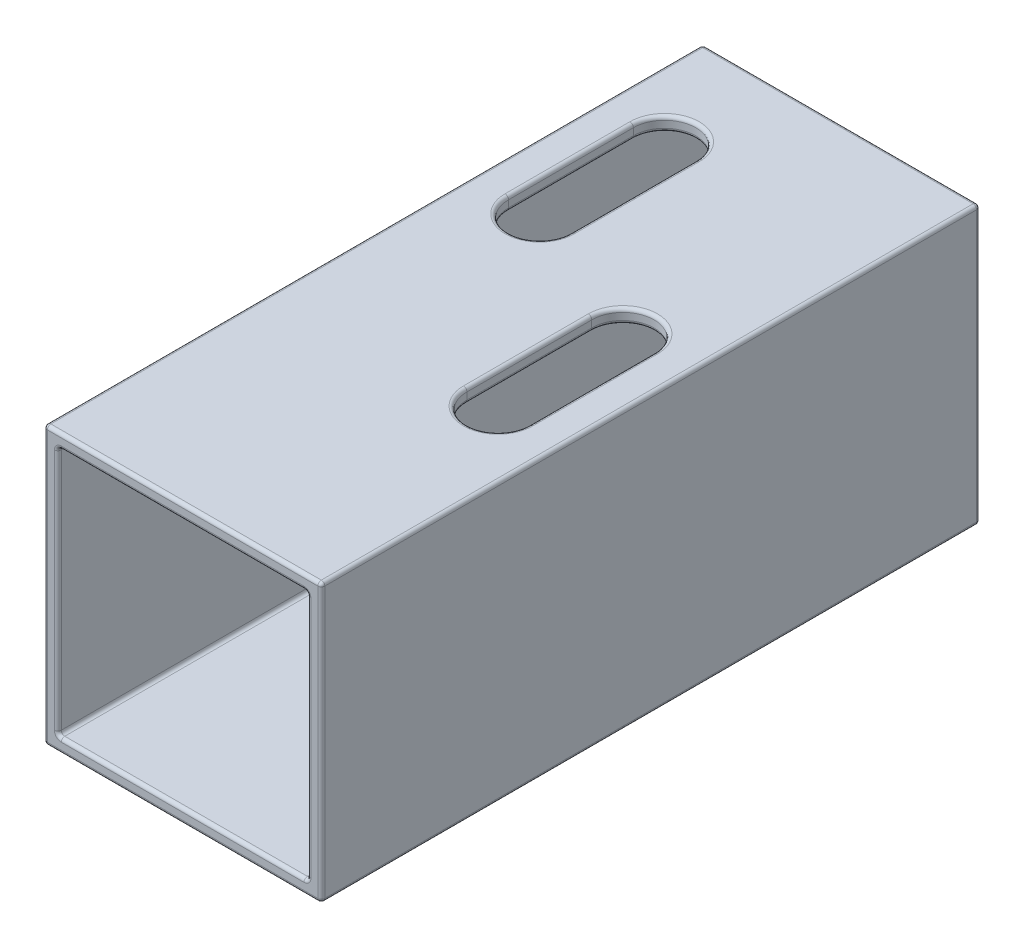
SolidWorks part; units mm, degrees
material "6061 Legierung"
ref_plane "Ebene vorne" through (0, 0, 0) normal (0, 0, 1) x (1, 0, 0)
ref_plane "Ebene oben" through (0, 0, 0) normal (0, 1, 0) x (1, 0, 0)
ref_plane "Ebene rechts" through (0, 0, 0) normal (1, 0, 0) x (0, 0, -1)
sketch "Skizze1" plane through (0, 0, 0) normal (0, 0, 1) x (1, 0, 0)
  line L1 (-20, -20) -> (20, -20)
  line L2 (-20, -20) -> (-20, 20)
  line L3 (-20, 20) -> (20, 20)
  line L4 (20, -20) -> (20, 20)
  line L5 (-20, -20) -> (20, 20) construction
  line L6 (-20, 20) -> (20, -20) construction
  line L7 (-18, -18) -> (18, -18)
  line L8 (-18, -18) -> (-18, 18)
  line L9 (-18, 18) -> (18, 18)
  line L10 (18, -18) -> (18, 18)
  line L11 (-18, -18) -> (18, 18) construction
  line L12 (-18, 18) -> (18, -18) construction
  point P0 (0, 0)
  point P6 (0, 0)
  dimension "D1" = 40
  dimension "D2" = 40
  dimension "D3" = 36
extrude "Aufsatz-Linear austragen1" add sketch "Skizze1" along normal blind 232
sketch "Skizze4" plane through (-20, 0, 0) normal (-1, 0, 0) x (0, 0, 1)
  line L1 (232, -34.3396) -> (95, -34.3396)
  line L2 (232, -34.3396) -> (232, 27.552)
  line L3 (232, 27.552) -> (95, 27.552)
  line L4 (95, -34.3396) -> (95, 27.552)
  line L5 (232, 20) -> (232, -20) construction
  dimension "D2" = 137
extrude "Schnitt-Linear austragen2" cut sketch "Skizze4" against normal through all
sketch "Skizze9" plane through (0, 20, 0) normal (0, 1, 0) x (1, 0, 0)
  line L1 (6, -37.5) -> (15, -37.5)
  line L2 (6, -37.5) -> (6, -64.5)
  line L3 (6, -64.5) -> (15, -64.5)
  line L4 (15, -37.5) -> (15, -64.5)
  line L7 (20, -95) -> (20, 0) construction
  line L8 (-20, -95) -> (20, -95) construction
  dimension "D1" = 9
  dimension "D2" = 5
  dimension "D3" = 57.5
  dimension "D4" = 30.5
extrude "Schnitt-Linear austragen5" cut sketch "Skizze9" against normal through all
fillet "Verrundung1" 2 edges at (6, 19, 37.5) (15, 19, 37.5) type full round first side face at (6, 19, 51) second side face at (15, 19, 51) middle face at (10.5, 19, 37.5)
fillet "Verrundung2" 2 edges at (15, 19, 64.5) (6, 19, 64.5) type full round first side face at (15, 19, 53.25) second side face at (6, 19, 53.25) middle face at (10.5, 19, 64.5)
fillet "Verrundung3" 2 edges at (15, -19, 64.5) (6, -19, 64.5) type full round first side face at (15, -19, 51) second side face at (6, -19, 51) middle face at (10.5, -19, 64.5)
fillet "Verrundung4" 2 edges at (15, -19, 37.5) (6, -19, 37.5) type full round first side face at (15, -19, 48.75) second side face at (6, -19, 48.75) middle face at (10.5, -19, 37.5)
sketch "Skizze10" plane through (0, 20, 0) normal (0, 1, 0) x (1, 0, 0)
  line L3 (-20, -95) -> (-20, 0) construction
  line L4 (-15, -10.5) -> (-6, -10.5)
  line L5 (-15, -10.5) -> (-15, -37.5)
  line L6 (-15, -37.5) -> (-6, -37.5)
  line L7 (-6, -10.5) -> (-6, -37.5)
  line L8 (20, 0) -> (-20, 0) construction
  dimension "D1" = 5
  dimension "D2" = 9
  dimension "D3" = 37.5
  dimension "D4" = 10.5
extrude "Schnitt-Linear austragen6" cut sketch "Skizze10" against normal through all
fillet "Verrundung5" 2 edges at (-15, 19, 10.5) (-6, 19, 10.5) type full round first side face at (-15, 19, 24) second side face at (-6, 19, 24) middle face at (-10.5, 19, 10.5)
fillet "Verrundung6" 2 edges at (-6, 19, 37.5) (-15, 19, 37.5) type full round first side face at (-6, 19, 26.25) second side face at (-15, 19, 26.25) middle face at (-10.5, 19, 37.5)
fillet "Verrundung7" 2 edges at (-6, -19, 37.5) (-15, -19, 37.5) type full round first side face at (-6, -19, 24) second side face at (-15, -19, 24) middle face at (-10.5, -19, 37.5)
fillet "Verrundung8" 2 edges at (-6, -19, 10.5) (-15, -19, 10.5) type full round first side face at (-6, -19, 21.75) second side face at (-15, -19, 21.75) middle face at (-10.5, -19, 10.5)
fillet "Verrundung9" radius 0.5 56 edges at (18, 0, 0) (18, 0, 95) (0, -18, 0) (18, -18, 47.5) (0, -18, 95) (10.5, -18, 64.5) (15, -18, 51) (10.5, -18, 37.5) (6, -18, 51) (-10.5, -18, 37.5) (-6, -18, 24) (-10.5, -18, 10.5) (-15, -18, 24) (18, 18, 47.5) (0, 18, 0) (0, 18, 95) (10.5, 18, 37.5) (15, 18, 51) (10.5, 18, 64.5) (6, 18, 51) (-10.5, 18, 10.5) (-6, 18, 24) (-10.5, 18, 37.5) (-15, 18, 24) (-18, 18, 47.5) (-18, 0, 0) (-18, -18, 47.5) (-18, 0, 95) (20, 0, 0) (20, 0, 95) (0, -20, 0) (0, -20, 95) (20, -20, 47.5) (15, -20, 51) (10.5, -20, 64.5) (6, -20, 51) (10.5, -20, 37.5) (-6, -20, 24) (-10.5, -20, 37.5) (-15, -20, 24) (-10.5, -20, 10.5) (-20, 0, 0) (-20, 0, 95) (-20, -20, 47.5) (0, 20, 0) (20, 20, 47.5) (0, 20, 95) (-20, 20, 47.5) (15, 20, 51) (10.5, 20, 37.5) (6, 20, 51) (10.5, 20, 64.5) (-6, 20, 24) (-10.5, 20, 10.5) (-15, 20, 24) (-10.5, 20, 37.5)
